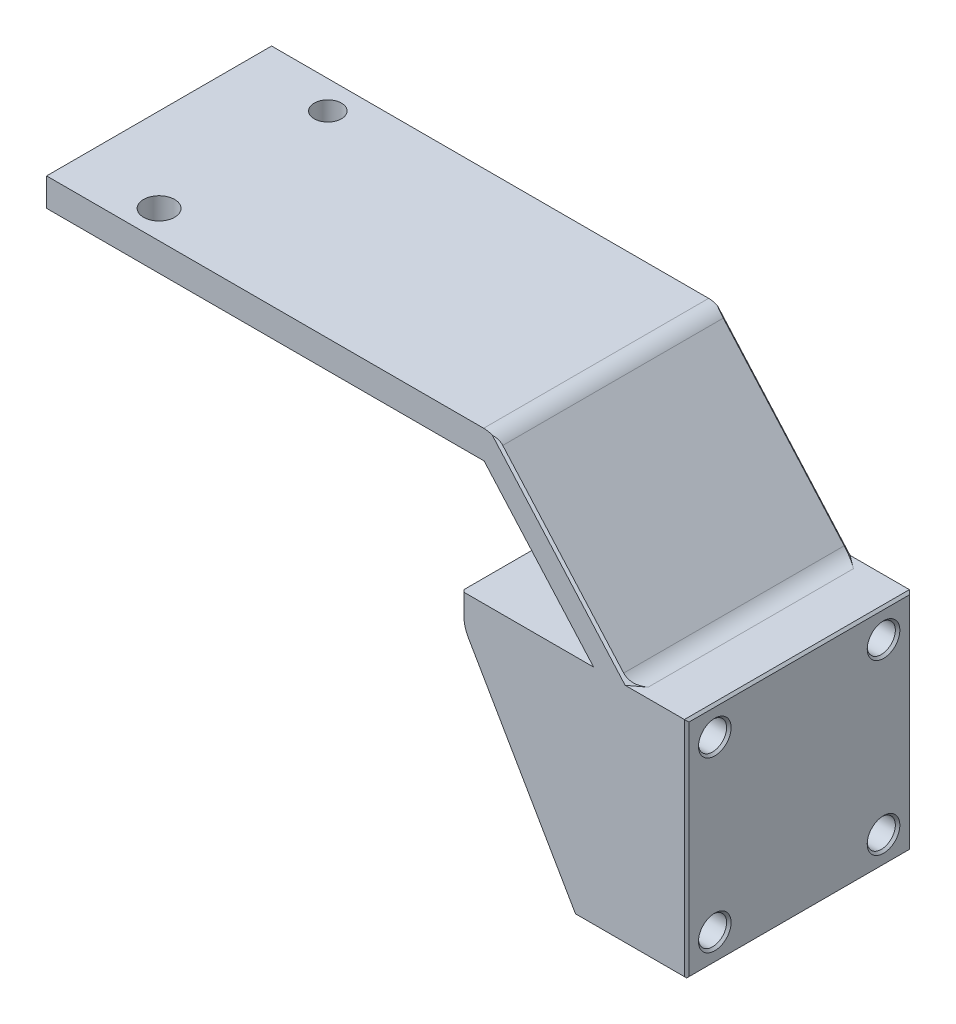
SolidWorks part; units mm, degrees
material "1060 Alloy"
ref_plane "Front Plane" through (0, 0, 0) normal (0, 0, 1) x (1, 0, 0)
ref_plane "Top Plane" through (0, 0, 0) normal (0, 1, 0) x (1, 0, 0)
ref_plane "Right Plane" through (0, 0, 0) normal (1, 0, 0) x (0, 0, -1)
sketch "Sketch1" plane through (0, 0, 0) normal (0, 0, 1) x (1, 0, 0)
  line L1 (-25.4, -25.4) -> (25.4, -25.4)
  line L2 (-25.4, -25.4) -> (-25.4, 25.4)
  line L3 (-25.4, 25.4) -> (25.4, 25.4)
  line L4 (25.4, -25.4) -> (25.4, 25.4)
  line L5 (-25.4, -25.4) -> (25.4, 25.4) construction
  line L6 (-25.4, 25.4) -> (25.4, -25.4) construction
  point P0 (0, 0)
  dimension "D1" = 50.8
  dimension "D2" = 50.8
extrude "Boss-Extrude1" add sketch "Sketch1" along normal blind 50.8
sketch "Sketch2" plane through (0, 0, 50.8) normal (0, 0, 1) x (1, 0, 0)
  line L0 (-25.4, 18.5941) -> (0, -25.4)
  line L1 (-25.4, 25.4) -> (-25.4, -25.4) construction
  line L2 (-25.4, -25.4) -> (25.4, -25.4) construction
  line L3 (0, -25.4) -> (-25.4, -25.4)
  line L4 (-25.4, -25.4) -> (-25.4, 18.5941)
  dimension "D1" = 60
  dimension "D2" = 50.8
extrude "Cut-Extrude1" cut sketch "Sketch2" against normal blind 50.8
sketch "Sketch4" plane through (25.4, 0, 0) normal (1, 0, 0) x (0, 0, -1)
  line L0 (-44.45, 19.05) -> (-6.35, 19.05) construction
  line L1 (-6.35, 19.05) -> (-6.35, -19.05) construction
  line L2 (-6.35, -19.05) -> (-44.45, -19.05) construction
  line L3 (-44.45, -19.05) -> (-44.45, 19.05) construction
  line L4 (-44.45, 19.05) -> (-6.35, -19.05) construction
  line L5 (-6.35, 19.05) -> (-44.45, -19.05) construction
  line L6 (-50.8, 25.4) -> (0, -25.4) construction
  line L7 (0, 25.4) -> (-50.8, -25.4) construction
  circle A0 centre (-44.45, 19.05) radius 3.175
  circle A1 centre (-6.35, 19.05) radius 3.175
  circle A2 centre (-6.35, -19.05) radius 3.175
  circle A3 centre (-44.45, -19.05) radius 3.175
  point P16 (-25.4, 0)
  point P17 (-25.4, 0)
  dimension "D1" = 6.35
  dimension "D2" = 38.1
extrude "Cut-Extrude2" cut sketch "Sketch4" against normal blind 12.7
sketch "Sketch5" plane through (-10.9985, -6.35, 0) normal (-0.866, -0.5, 0) x (0, 0, 1)
  line L0 (6.35, 22.453) -> (6.35, -15.647) construction
  line L1 (6.35, -15.647) -> (44.45, -15.647) construction
  line L2 (44.45, -15.647) -> (44.45, 22.453) construction
  line L3 (44.45, 22.453) -> (6.35, 22.453) construction
  line L4 (6.35, 22.453) -> (44.45, -15.647) construction
  line L5 (44.45, 22.453) -> (6.35, -15.647) construction
  line L6 (0, 28.803) -> (50.8, -21.997) construction
  line L7 (50.8, 28.803) -> (0, -21.997) construction
  circle A0 centre (6.35, 22.453) radius 3.175
  circle A1 centre (44.45, 22.453) radius 3.175
  circle A2 centre (44.45, -15.647) radius 3.175
  circle A3 centre (6.35, -15.647) radius 3.175
  point P14 (25.4, 3.403)
  point P17 (25.4, 3.403)
  dimension "D2" = 6.35
  dimension "D1" = 38.1
extrude "Cut-Extrude3" cut sketch "Sketch5" against normal blind 12.7
chamfer "Chamfer1" distance 0.508 angle 45 8 edges at (25.4, 25.4, 25.4) (25.4, 0, 0) (25.4, -25.4, 25.4) (25.4, 0, 50.8) (25.4, 19.05, 41.275) (25.4, 19.05, 3.175) (25.4, -19.05, 3.175) (25.4, -19.05, 41.275)
chamfer "Chamfer3" distance 0.508 angle 45 5 edges at (0, -25.4, 25.4) (-1.5875, -22.6504, 44.45) (-20.6375, 10.3452, 44.45) (-20.6375, 10.3452, 6.35) (-1.5875, -22.6504, 6.35) first distance on face at (12.446, -25.4, 25.4) first distance on face at (-1.5875, -22.6504, 6.35)
fillet "Fillet3" radius 7.62 1 edges at (-25.4, 18.5941, 25.4)
sketch "Sketch6" plane through (0, 0, 0) normal (0, 0, -1) x (-1, 0, 0)
  line L0 (-12.192, 25.4) -> (18.1454, 59.69)
  line L1 (-24.892, 25.4) -> (25.4, 25.4) construction
  line L2 (18.1454, 59.69) -> (119.1179, 59.69)
  line L3 (119.1179, 59.69) -> (119.1179, 53.34)
  line L4 (119.1179, 53.34) -> (21.0059, 53.34)
  line L5 (21.0059, 53.34) -> (-3.7135, 25.4)
  line L6 (25.4, 25.4) -> (-3.7135, 25.4)
  line L7 (-12.192, 25.4) -> (-3.7135, 25.4)
  line L12 (0.6939, -24.1981) -> (24.3791, 16.8259)
  line L13 (25.4, 20.6359) -> (25.4, 25.4)
  line L14 (25.4, 25.4) -> (-24.892, 25.4)
  line L15 (-24.892, 25.4) -> (-24.892, -25.4)
  line L16 (-24.892, -25.4) -> (-0.508, -25.4)
  line L17 (-0.508, -25.4) -> (0.6939, -24.1981)
  line L18 (0.6939, -24.1981) -> (24.3791, 16.8259)
  line L19 (25.4, 20.6359) -> (25.4, 25.4)
  line L20 (-12.192, 25.4) -> (-24.892, 25.4)
  line L21 (-24.892, 25.4) -> (-24.892, -25.4)
  line L22 (-24.892, -25.4) -> (-0.508, -25.4)
  line L23 (-0.508, -25.4) -> (0.6939, -24.1981)
  arc A1 (24.3791, 16.8259) -> (25.4, 20.6359) centre (17.78, 20.6359) ccw
  arc A2 (24.3791, 16.8259) -> (25.4, 20.6359) centre (17.78, 20.6359) ccw
  line M4 (25.4, 25.4) -> (-24.892, 25.4)
  dimension "D1" = 27.94
  dimension "D2" = 6.35
  dimension "D3" = 6.35
  dimension "D4" = 12.7
  dimension "D5" = 0
extrude "Boss-Extrude2" add sketch "Sketch6" against normal through all contours L5 L4 L3 L2 L0 M4 region at (-3.9931, 41.6457, 0)
chamfer "Chamfer4" distance 0.508 angle 45 8 edges at (12.7, -25.4, 0) (12.7, -25.4, 50.8) (-25.4, 23.0179, 50.8) (-25.1404, 18.6637, 50.8) (-12.5365, -3.6861, 50.8) (-25.4, 23.0179, 0) (-25.1404, 18.6637, 0) (-12.5365, -3.6861, 0)
chamfer "Chamfer5" distance 0.508 angle 45 4 edges at (-8.6462, 39.37, 50.8) (-8.6462, 39.37, 0) (-2.9767, 42.545, 50.8) (-2.9767, 42.545, 0)
sketch "Sketch7" plane through (0, 59.69, 0) normal (0, 1, 0) x (1, 0, 0)
  line L2 (-119.1179, -50.8) -> (-119.1179, 0) construction
  line L3 (-18.8237, 0) -> (-119.1179, 0) construction
  circle A0 centre (-100.0679, -6.35) radius 3.0799
  circle A1 centre (-100.0679, -44.45) radius 3.5049
  dimension "D1" = 38.1
  dimension "D2" = 6.35
  dimension "D3" = 19.05
extrude "Cut-Extrude4" cut sketch "Sketch7" against normal blind 19.05
sketch "Sketch9" plane through (0, 53.34, 0) normal (0, -1, 0) x (-1, 0, 0)
  line L0 (119.1179, -50.8) -> (119.1179, 0) construction
  line L1 (81.0179, -22.225) -> (21.0059, -22.225)
  line L2 (81.0179, -22.225) -> (81.0179, -28.575)
  line L3 (81.0179, -28.575) -> (21.0059, -28.575)
  line L4 (21.0059, -22.225) -> (21.0059, -28.575)
  line L5 (119.1179, 0) -> (20.3276, 0) construction
  line L6 (21.0059, -50.292) -> (21.0059, -0.508) construction
  dimension "D1" = 38.1
  dimension "D2" = 6.35
  dimension "D3" = 22.225
extrude "Boss-Extrude4" add sketch "Sketch9" along normal blind 12.7
sketch "Sketch10" plane through (14.6884, 12.9952, 0) normal (-0.749, -0.6626, 0) x (0, 0, 1)
  line L0 (28.575, 53.8681) -> (28.575, 16.5628)
  line L1 (50.292, 16.5628) -> (0.508, 16.5628) construction
  line L2 (28.575, 16.5628) -> (22.225, 16.5628)
  line L3 (22.225, 16.5628) -> (22.225, 53.8681)
  line L4 (22.225, 53.8681) -> (28.575, 53.8681)
extrude "Boss-Extrude5" add sketch "Sketch10" along normal blind 12.7
fillet "Fillet6" radius 5.08 11 edges at (-51.0119, 53.34, 22.225) (-8.6462, 39.37, 22.225) (-8.6462, 39.37, 28.575) (-51.0119, 53.34, 28.575) (-13.2435, 25.4, 25.4) (3.7135, 25.4, 39.4335) (3.7135, 25.4, 11.3665) (-21.0059, 53.34, 39.4335) (-21.0059, 53.34, 11.3665) (-18.1454, 59.69, 25.4) (12.192, 25.4, 25.4)
